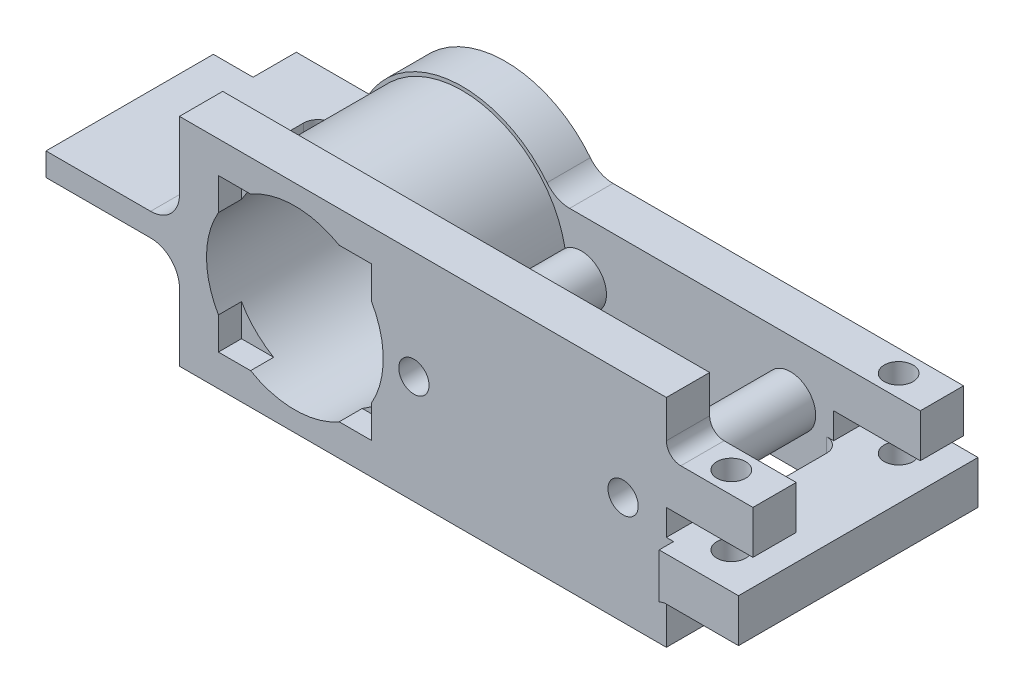
SolidWorks part; units mm, degrees
ref_plane "Front Plane" through (0, 0, 0) normal (0, 0, 1) x (1, 0, 0)
ref_plane "Top Plane" through (0, 0, 0) normal (0, 1, 0) x (1, 0, 0)
ref_plane "Right Plane" through (0, 0, 0) normal (1, 0, 0) x (0, 0, -1)
sketch "Sketch1" plane through (0, 0, 0) normal (0, 0, 1) x (1, 0, 0)
  line L1 (-20, 7.5) -> (20, 7.5)
  line L2 (-20, 7.5) -> (-20, -7.5)
  line L3 (-20, -7.5) -> (20, -7.5)
  line L4 (20, 7.5) -> (20, -7.5)
  line L5 (-20, 7.5) -> (20, -7.5) construction
  line L6 (-20, -7.5) -> (20, 7.5) construction
  point P0 (0, 0)
  dimension "D1" = 40
  dimension "D2" = 15
extrude "Boss-Extrude1" add sketch "Sketch1" along normal mid plane 3
sketch "Sketch2" plane through (0, 0, -1.5) normal (0, 0, 1) x (1, 0, 0)
  line L0 (15.75, -6.25) -> (15.75, 6.25) construction
  line L1 (15.75, -6.25) -> (15.75, 6.25)
  line L2 (-15, -7) -> (15, -7) construction
  line L3 (15, 7) -> (-15, 7) construction
  line L4 (-15, -7) -> (15, -7)
  line L5 (15, 7) -> (-15, 7)
  line L6 (-15.75, 6.25) -> (-15.75, -6.25) construction
  line L7 (-15.75, 6.25) -> (-15.75, -6.25)
  line L8 (-13.75, 5) -> (-3.75, 5) construction
  line L9 (-13.75, 5) -> (-13.75, -5) construction
  line L10 (-13.75, -5) -> (-3.75, -5) construction
  line L11 (-13.75, 5) -> (-3.75, 5) construction
  line L12 (-13.75, 5) -> (-13.75, -5) construction
  line L13 (-13.75, -5) -> (-3.75, -5) construction
  line L14 (-3.75, 5) -> (-3.75, -5) construction
  line L15 (-3.75, 5) -> (-3.75, -5) construction
  arc A1 (15, -7) -> (15.75, -6.25) centre (15, -6.25) ccw construction
  arc A2 (15.75, 6.25) -> (15, 7) centre (15, 6.25) ccw construction
  arc A3 (15, -7) -> (15.75, -6.25) centre (15, -6.25) ccw
  arc A4 (15.75, 6.25) -> (15, 7) centre (15, 6.25) ccw
  arc A5 (-15.75, -6.25) -> (-15, -7) centre (-15, -6.25) ccw construction
  arc A6 (-15, 7) -> (-15.75, 6.25) centre (-15, 6.25) ccw construction
  arc A7 (-15.75, -6.25) -> (-15, -7) centre (-15, -6.25) ccw
  arc A8 (-15, 7) -> (-15.75, 6.25) centre (-15, 6.25) ccw
  circle A9 centre (-0.5, 0) radius 1.1 construction
  circle A10 centre (14, 0) radius 1.1 construction
  circle A11 centre (-0.5, 0) radius 1.1 construction
  circle A12 centre (14, 0) radius 1.1 construction
  circle A13 centre (-8.75, 0) radius 6.125
  circle A14 centre (-0.5, 0) radius 1.05
  circle A15 centre (14, 0) radius 1.05
  point P24 (-8.75, -5)
  dimension "D1" = 12.25
  dimension "D2" = 2.1
sketch "Sketch3" plane through (0, 0, -1.5) normal (0, 0, -1) x (-1, 0, 0)
  line L0 (-20, -0.9) -> (-17, -0.9)
  line L1 (-20, -7.5) -> (-20, 7.5) construction
  line L2 (-17, -0.9) -> (-17, 0.9)
  line L3 (-17, 0.9) -> (-20, 0.9)
  line L4 (-20, -0.9) -> (-20, 0.9)
  line L5 (-17, -7.5) -> (-17, -3.9)
  line L6 (20, -7.5) -> (-20, -7.5) construction
  line L7 (-17, -3.9) -> (-20, -3.9)
  line L8 (-20, -3.9) -> (-20, -7.5)
  line L9 (-20, -7.5) -> (-17, -7.5)
  line L10 (-20, 7.5) -> (-20, 3.9)
  line L11 (-20, 3.9) -> (-17, 3.9)
  line L12 (-17, 3.9) -> (-17, 7.5)
  line L13 (-20, 7.5) -> (20, 7.5) construction
  line L14 (-17, 7.5) -> (-20, 7.5)
  point P4 (-20, 0)
  point P7 (-20, 0)
  dimension "D1" = 1.8
  dimension "D2" = 3
  dimension "D3" = 3
  dimension "D4" = 3
extrude "Cut-Extrude1" cut sketch "Sketch3" against normal through all
extrude "Cut-Extrude2" cut sketch "Sketch2" along normal through all contours A11 | A12 | L11 L12 L13 L15 | A13 | A14 | A15
sketch "Sketch4" plane through (0, 0, -1.5) normal (0, 0, -1) x (-1, 0, 0)
  line L0 (20, -7.5) -> (20, 7.5)
  line L1 (20, 7.5) -> (23, 7.5)
  line L3 (23, -7.5) -> (20, -7.5)
  line L4 (-20, -3.9) -> (-23, -3.9)
  line L5 (-23, -3.9) -> (-23, -0.9)
  line L6 (-23, -0.9) -> (-20, -0.9)
  line L7 (-20, -0.9) -> (-20, -3.9)
  line L8 (-20, 0.9) -> (-23, 0.9)
  line L9 (-23, 0.9) -> (-23, 3.9)
  line L10 (-23, 3.9) -> (-20, 3.9)
  line L11 (-20, 3.9) -> (-20, 0.9)
  line L13 (26, -0.8) -> (23, -0.8)
  line L14 (23, -0.8) -> (23, -7.5031)
  line L15 (26, 0.8) -> (23, 0.8)
  line L16 (23, 0.8) -> (23, 7.5)
  line L17 (26, -0.8) -> (26, 0.8)
  point P4 (26, 0)
  line M15 (-20, 3.9) -> (-20, 0.9)
  line M19 (-20, -0.9) -> (-20, -3.9)
  line M23 (20, -7.5) -> (20, 7.5)
  dimension "D1" = 3
  dimension "D2" = 49
  dimension "D3" = 3
  dimension "D4" = 1.6
extrude "Boss-Extrude2" add sketch "Sketch4" against normal up to surface (3 mm away) contours L13 L17 L15 L16 L1 L3 L14 M23 | L6 L5 L4 M19 | L10 L9 L8 M15 region at (-21.7892, 0, -1.5) region at (21.5, -2.4, -1.5) region at (21.5, 2.4, -1.5) up to face at (-2.625, 0, 1.5)
sketch "Sketch5" plane through (0, -3.9, 0) normal (0, -1, 0) x (1, 0, 0)
  line L0 (17, 1.5) -> (23, 1.5) construction
  line L1 (23, 1.5) -> (23, -1.5) construction
  point P0 (20, 0)
  point P3 (20, 1.5)
  point P8 (23, 0)
sketch "Sketch8" plane through (0, 0, -1.5) normal (0, 0, -1) x (-1, 0, 0)
  line L1 (26, -0.8) -> (23, -0.8)
  line L2 (26, -0.8) -> (26, 0.8)
  line L3 (26, 0.8) -> (23, 0.8)
  line L4 (23, -0.8) -> (23, 0.8)
extrude "Boss-Extrude3" add sketch "Sketch8" along normal blind 8.6
sketch "Sketch9" plane through (0, 0, -10.1) normal (0, 0, -1) x (-1, 0, 0)
  line L0 (26, 0.8) -> (23, 0.8) construction
  line L1 (26, -0.8) -> (16.2072, -0.8)
  line L2 (26, -0.8) -> (26, 0.8)
  line L3 (26, 0.8) -> (16.2072, 0.8)
  line L5 (-23, 3.9) -> (2.3438, 3.9)
  line L6 (-23, 3.9) -> (-23, 0.9)
  line L7 (-23, -3.9) -> (2.3438, -3.9)
  line L9 (-17, -3.9) -> (-23, -3.9) construction
  line L10 (-23, 3.9) -> (-17, 3.9) construction
  line L11 (-23, -3.9) -> (-23, -0.9) construction
  line L12 (-23, -0.9) -> (-17, -0.9) construction
  line L13 (-23, -0.9) -> (-17, -0.9)
  line L15 (-23, 0.9) -> (-17, 0.9)
  line L16 (-17, -0.9) -> (-17, 0.9)
  line L17 (-17, -0.9) -> (-17, 0.9) construction
  line L18 (-17, 0.9) -> (-23, 0.9) construction
  line L19 (-23, -0.9) -> (-23, -3.9)
  arc A0 (16.2072, 0.8) -> (2.3438, 3.9) centre (8.75, 0) ccw
  circle A1 centre (8.75, 0) radius 6.125 construction
  arc A2 (2.3438, -3.9) -> (16.2072, -0.8) centre (8.75, 0) ccw
  circle A4 centre (0.5, 0) radius 1.05
  circle A6 centre (-14, 0) radius 1.05
  circle A7 centre (0.5, 0) radius 1.05 construction
  circle A8 centre (-14, 0) radius 1.05 construction
  dimension "D1" = 15
extrude "Boss-Extrude4" add sketch "Sketch9" along normal blind 3
sketch "Sketch10" plane through (0, 0, -13.1) normal (0, 0, -1) x (-1, 0, 0)
  point P0 (8.75, 0)
hole_wizard "M1.6 Clearance Hole2" positions "Sketch6" profile "Sketch7" hole size "M1.6" standard "ANSI Metric" end condition through all
sketch "Sketch6" plane through (0, -3.9, 0) normal (0, -1, 0) x (-1, 0, 0)
  line L0 (-23, 13.1) -> (-23, 10.1) construction
  point P0 (-20, 0)
  point P3 (-20, 11.6)
  point P8 (-23, 11.6)
sketch "Sketch7" plane through (20, -3.9, 0) normal (1, 0, 0) x (0, 0, -1)
  line L0 (0, 0) -> (0, 11.4)
  line L1 (0, 11.4) -> (1, 11.4)
  line L2 (1, 11.4) -> (1, 0)
  line L5 (1, 0) -> (0, 0)
  line L11 (0, -6.35) -> (0, 107.95) construction
  dimension "Thru Hole Dia." = 2
  dimension "Thru Hole Depth" = 11.4
sketch "Sketch13" plane through (0, 0, -1.5) normal (0, 0, -1) x (-1, 0, 0)
  line L0 (23, -7.5) -> (-17, -7.5) construction
  line L1 (23, -0.8) -> (16.75, -0.8)
  line L2 (23, -0.8) -> (23, -7.5)
  line L3 (23, -7.5) -> (16.75, -7.5)
  line L4 (16.75, -0.8) -> (16.75, -7.5)
  line L5 (23, 0.8) -> (23, 7.5) construction
  line L6 (23, 0.8) -> (16.75, 0.8)
  line L7 (23, 0.8) -> (23, 7.5)
  line L8 (23, 7.5) -> (16.75, 7.5)
  line L9 (16.75, 0.8) -> (16.75, 7.5)
  line L10 (-17, 7.5) -> (23, 7.5) construction
  line L11 (26, 0.8) -> (23, 0.8) construction
  line L12 (15.75, 6.25) -> (15.75, -6.25) construction
  dimension "D1" = 1
extrude "Cut-Extrude3" cut sketch "Sketch13" against normal blind 3
sketch "Sketch14" plane through (0, 0, -1.5) normal (0, 0, -1) x (-1, 0, 0)
  arc A0 (1.625, 1.3405) -> (1.625, -1.3405) centre (0.5, 0) ccw
  circle A1 centre (-14, 0) radius 1.75
  circle A2 centre (0.5, 0) radius 1.05
  circle A3 centre (-14, 0) radius 1.05
  arc A6 (1.5062, -0.3001) -> (1.5062, 0.3001) centre (8.75, 0) ccw
  circle A7 centre (0.5, 0) radius 1.05 construction
  circle A8 centre (-14, 0) radius 1.05 construction
  circle M3 centre (8.75, 0) radius 6.125
  dimension "D1" = 3.5
  dimension "D2" = 14.5
extrude "Boss-Extrude5" add sketch "Sketch14" along normal up to surface (8.6 mm away) contours A6 A2 M3 | A6 A0 | A1 region at (-1.5018, 0.8276, -1.5) region at (-15.795, 0, -1.5) region at (15.7005, 0, -1.5) up to face at (-1.55, 0, -10.1)
sketch "Sketch15" plane through (0, -0.8, 0) normal (0, -1, 0) x (1, 0, 0)
  line L0 (-16.2072, -10.1) -> (-23, -10.1) construction
  line L1 (-23, -1.5) -> (-18.75, -1.5)
  line L2 (-23, -1.5) -> (-23, -10.1)
  line L3 (-23, -10.1) -> (-18.75, -10.1)
  line L4 (-18.75, -1.5) -> (-18.75, -10.1)
  dimension "D1" = 4.25
extrude "Boss-Extrude6" add sketch "Sketch15" against normal up to surface (1.6 mm away) up to face at (-20.4893, 0.8, -5.8)
hole_wizard "M12x1.25 Tapped Hole1" positions "Sketch11" profile "Sketch12" tap size "M12x1.25" standard "ANSI Metric" end condition through all
sketch "Sketch11" plane through (0, 0, -13.1) normal (0, 0, -1) x (-1, 0, 0)
  point P0 (8.75, 0)
cosmetic thread "Hole Thread1" parameters "D2"=12
sketch "Sketch12" plane through (-8.75, 0, -13.1) normal (1, 0, 0) x (0, 1, 0)
  line L0 (0, 0) -> (0, 14.6)
  line L1 (0, 14.6) -> (6, 14.6)
  line L2 (6, 14.6) -> (6, 0)
  line L5 (6, 0) -> (0, 0)
  line L11 (0, -6.35) -> (0, 107.95) construction
  dimension "Thru Tap Drill Dia." = 12
  dimension "Thru Tap Drill Depth" = 14.6
fillet "Fillet1" radius 2 6 edges at (-2.3438, 3.9, -11.6) (-2.3438, -3.9, -11.6) (-16.2072, 0.8, -11.6) (-16.2072, -0.8, -11.6) (-16.75, 0.8, 0) (-16.75, -0.8, 0)
sketch "Sketch16" plane through (0, -3.9, 0) normal (0, -1, 0) x (1, 0, 0)
  line L0 (17, -1.5) -> (23, -1.5) construction
  line L1 (23, -10.1) -> (17.5, -10.1)
  line L2 (23, -10.1) -> (23, -1.5)
  line L3 (23, -1.5) -> (17.5, -1.5)
  line L4 (17.5, -10.1) -> (17.5, -1.5)
  line L5 (23, -13.1) -> (17.5, -13.1)
  line L6 (23, -13.1) -> (23, -14.1)
  line L7 (23, -14.1) -> (17.5, -14.1)
  line L8 (17.5, -13.1) -> (17.5, -14.1)
  line L9 (23, 1.5) -> (17.5, 1.5)
  line L10 (23, 1.5) -> (23, 2.5)
  line L11 (23, 2.5) -> (17.5, 2.5)
  line L12 (17.5, 1.5) -> (17.5, 2.5)
  dimension "D1" = 5.5
  dimension "D2" = 1
extrude "Boss-Extrude7" add sketch "Sketch16" against normal up to surface (3 mm away) up to face at (20, -0.9, -12.6)
fillet "Fillet2" radius 1 2 edges at (-18.75, 0, -10.1) (-18.75, 0, -1.5)
fillet "Fillet3" radius 1 4 edges at (17.5, -2.4, -13.1) (17.5, -2.4, -10.1) (17, 3.9, 0) (17, -3.9, 0)
fillet "Fillet4" radius 1 1 edges at (17.5, -2.4, -1.5)
sketch "Sketch17" plane through (0, 0.8, 0) normal (0, 1, 0) x (1, 0, 0)
  line L0 (-26, 13.1) -> (-26, 10.1)
  line L5 (-26, -1.5) -> (-26, 13.1) construction
  line L6 (-26, 10.1) -> (-23.25, 10.1)
  line L7 (-23.25, 10.1) -> (-23.25, 13.1)
  line L8 (-26, 13.1) -> (-17.828, 13.1) construction
  line L9 (-23.25, 13.1) -> (-26, 13.1)
  dimension "D1" = 3
  dimension "D2" = 2.75
extrude "Cut-Extrude4" cut sketch "Sketch17" against normal up to surface (1.6 mm away) up to face at (-20.5859, -0.8, -6.4396)
sketch "Sketch18" plane through (0, 0, 1.5) normal (0, 0, 1) x (1, 0, 0)
  line L1 (-14.05, 5.3) -> (-3.45, 5.3)
  line L2 (-14.05, 5.3) -> (-14.05, -5.3)
  line L3 (-14.05, -5.3) -> (-3.45, -5.3)
  line L4 (-3.45, 5.3) -> (-3.45, -5.3)
  line L5 (-14.05, 5.3) -> (-3.45, -5.3) construction
  line L6 (-14.05, -5.3) -> (-3.45, 5.3) construction
  point P0 (-8.75, 0)
  dimension "D1" = 10.6
extrude "Cut-Extrude5" cut sketch "Sketch18" against normal blind 1.6
